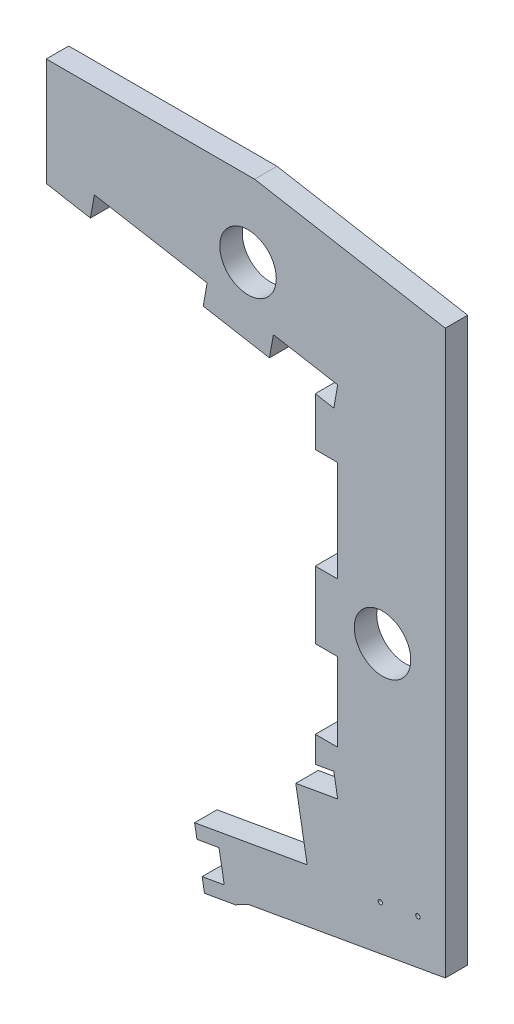
SolidWorks part; units mm, degrees
material "Balsa"
ref_plane "Plan de face" through (0, 0, 0) normal (0, 0, 1) x (1, 0, 0)
ref_plane "Plan de dessus" through (0, 0, 0) normal (0, 1, 0) x (1, 0, 0)
ref_plane "Plan de droite" through (0, 0, 0) normal (1, 0, 0) x (0, 0, -1)
sketch "Esquisse1" plane through (0, 0, 0) normal (0, 0, 1) x (1, 0, 0)
  line L0 (-65, 51.4613) -> (0, 40)
  line L1 (0, 40) -> (0, -40)
  line L2 (-6.8091, -56.1122) -> (-9.3591, -41.6503)
  line L3 (-9.3591, -41.6503) -> (0, -40)
  line L4 (-6.8091, -56.1122) -> (-31.9182, -60.5396)
  line L5 (-29.71, -73.063) -> (25, -63.4162)
  line L6 (25, -63.4162) -> (25, 63.8008)
  line L7 (25, 63.8008) -> (-18.4444, 71.4613)
  line L8 (-65, 71.4613) -> (-65, 51.4613)
  line L9 (7.1417, -5.2313) -> (92.0944, -5.2313) construction
  line L10 (-31.9182, -60.5396) -> (-29.71, -73.063)
  line L11 (-18.4444, 71.4613) -> (-65, 71.4613)
  line L12 (-18.4444, 71.4613) -> (-20, 53.6808) construction
  circle A0 centre (-20, 53.6808) radius 6.3
  circle A1 centre (10, -5) radius 6.3
  point P4 (-29.6197, 71.4613)
  point P19 (-7.4389, 69.5207)
  dimension "D1" = 12.6
  dimension "D15" = 12.6
  dimension "D2" = 10
  dimension "D3" = 20
  dimension "D4" = 80
  dimension "D5" = 65
  dimension "D6" = 100
  dimension "D7" = 100
  dimension "D8" = 85
  dimension "D9" = 35
  dimension "D10" = 90
  dimension "D11" = 9.5035
  dimension "D12" = 14.685
  dimension "D13" = 10
  dimension "D14" = 35
  dimension "D16" = 12.7166
  dimension "D17" = 100
  dimension "D18" = 100
  dimension "D19" = 20
extrude "Boss.-Extru.1" add sketch "Esquisse1" along normal blind 5
sketch "Esquisse2" plane through (0, 0, 0) normal (0, 0, -1) x (-1, 0, 0)
  line L0 (31.3966, -63.498) -> (30.231, -70.1086)
  line L1 (31.3966, -63.498) -> (26.4726, -62.6297)
  line L2 (30.231, -70.1086) -> (25.3069, -69.2404)
  line L3 (26.4726, -62.6297) -> (25.3069, -69.2404)
  line L5 (-16.8787, -72.4038) -> (-12.3995, -47.0007) construction
  line L11 (31.9182, -60.5396) -> (29.71, -73.063) construction
  line L12 (6.8091, -56.1122) -> (31.9182, -60.5396) construction
  circle A0 centre (-9.5242, -55.1691) radius 0.5
  circle A1 centre (-17.8951, -53.6931) radius 0.5
  dimension "D2" = 5
  dimension "D3" = 3.004
  dimension "D4" = 3
extrude "Enlèv. mat.-Extru.1" cut sketch "Esquisse2" against normal blind 5
sketch "Esquisse3" plane through (0, 0, 0) normal (0, 0, 1) x (1, 0, 0)
  line L0 (0, -40) -> (0, -30)
  line L1 (0, 40) -> (0, -40) construction
  line L2 (0, -40) -> (-9.3591, -41.6503) construction
  line L3 (0, -30) -> (-5, -30)
  line L4 (-5, -30) -> (-5, -35.8045)
  line L5 (-5, -35.8045) -> (-0.8682, -35.076)
  line L6 (-0.8682, -35.076) -> (0, -40)
  line L7 (0, 0) -> (-23.4139, 0) construction
  line L8 (0, 2.5) -> (-5, 2.5)
  line L9 (0, 2.5) -> (0, -12.5)
  line L10 (0, -12.5) -> (-5, -12.5)
  line L11 (-5, 2.5) -> (-5, -12.5)
  line L12 (0, 40) -> (0, -40) construction
  line L13 (-0.8682, 35.076) -> (0, 40)
  line L14 (-5, 35.8045) -> (-0.8682, 35.076)
  line L15 (-5, 25) -> (-5, 35.8045)
  line L16 (0, 25) -> (-5, 25)
  line L17 (0, 40) -> (0, 25)
  line L18 (-29.1225, 45.1351) -> (-14.3504, 42.5304)
  line L19 (-65, 51.4613) -> (0, 40) construction
  line L20 (-14.3504, 42.5304) -> (-15.2187, 37.6063)
  line L21 (-15.2187, 37.6063) -> (-29.9908, 40.2111)
  line L22 (-29.9908, 40.2111) -> (-29.1225, 45.1351)
  line L23 (-65, 51.4613) -> (-65, 46.3841)
  line L24 (-65, 46.3841) -> (-55.1519, 44.6476)
  line L25 (-55.1519, 44.6476) -> (-54.2837, 49.5717)
  line L26 (-54.2837, 49.5717) -> (-65, 51.4613)
  line L27 (-65, 71.4613) -> (-65, 51.4613) construction
  circle A0 centre (10, -5) radius 6.3 construction
  circle A1 centre (-20, 53.6808) radius 6.3 construction
  dimension "D1" = 10
  dimension "D2" = 5
  dimension "D3" = 5
  dimension "D4" = 10
  dimension "D5" = 5
  dimension "D6" = 7.5
  dimension "D7" = 15
  dimension "D8" = 15
  dimension "D9" = 5
  dimension "D10" = 15
  dimension "D11" = 7.5
  dimension "D12" = 5
  dimension "D13" = 10
extrude "Boss.-Extru.3" add sketch "Esquisse3" along normal blind 5
sketch "Esquisse4" plane through (0, 0, 5) normal (0, 0, 1) x (1, 0, 0)
  line L0 (-65, 70.4613) -> (-18.5319, 70.4613)
  line L1 (-65, 71.4613) -> (-65, 46.3841) construction
  line L2 (-18.5319, 70.4613) -> (24, 62.9617)
  line L3 (24, 62.9617) -> (24, -62.5771)
  line L4 (24, -62.5771) -> (-19.8968, -70.3173)
  line L5 (-19.8968, -70.3173) -> (-22.8293, -71.8498)
  line L6 (-29.71, -73.063) -> (25, -63.4162) construction
  line L7 (-65, 70.4613) -> (-65, 79.0214)
  line L8 (-65, 79.0214) -> (35.2298, 79.0214)
  line L9 (35.2298, 79.0214) -> (35.2298, -71.8498)
  line L10 (35.2298, -71.8498) -> (-22.8293, -71.8498)
  line L11 (-18.4444, 71.4613) -> (-65, 71.4613) construction
  line L12 (25, 63.8008) -> (-18.4444, 71.4613) construction
  line L13 (25, -63.4162) -> (25, 63.8008) construction
  dimension "D1" = 1
  dimension "D2" = 1
  dimension "D3" = 1
  dimension "D4" = 1
extrude "Enlèv. mat.-Extru.2" cut sketch "Esquisse4" against normal blind 5
